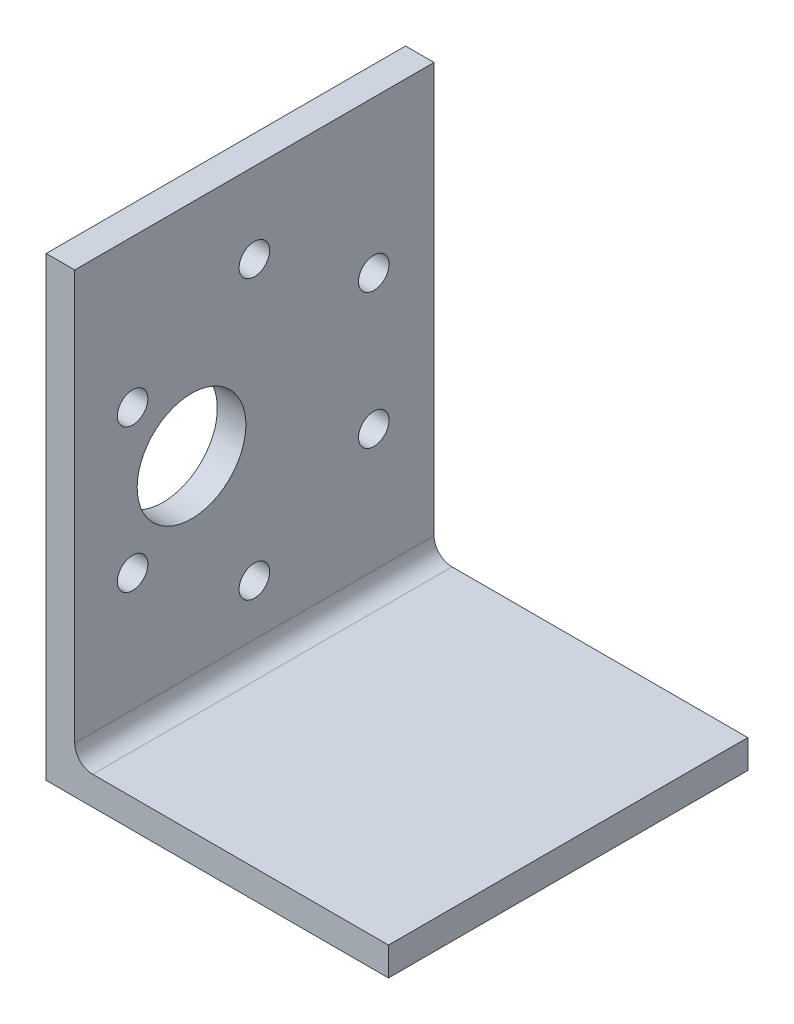
SolidWorks part; units mm, degrees
material "6061-T6 (SS)"
ref_plane "Front Plane" through (0, 0, 0) normal (0, 0, 1) x (1, 0, 0)
ref_plane "Top Plane" through (0, 0, 0) normal (0, 1, 0) x (1, 0, 0)
ref_plane "Right Plane" through (0, 0, 0) normal (1, 0, 0) x (0, 0, -1)
sketch "Sketch1" plane through (0, 0, 0) normal (0, 0, 1) x (1, 0, 0)
  line L0 (0, 0) -> (0, 50.8)
  line L1 (0, 50.8) -> (3.175, 50.8)
  line L2 (3.175, 50.8) -> (3.175, 3.175)
  line L3 (3.175, 3.175) -> (38.1, 3.175)
  line L4 (38.1, 3.175) -> (38.1, 0)
  line L5 (38.1, 0) -> (0, 0)
  dimension "D1" = 3.175
  dimension "D2" = 3.175
  dimension "D3" = 38.1
  dimension "D4" = 50.8
extrude "Boss-Extrude1" add sketch "Sketch1" along normal mid plane 40
fillet "Fillet1" radius 2 1 edges at (3.175, 3.175, 0)
sketch "Sketch10" plane through (0, 0, 0) normal (-1, 0, 0) x (0, 0, 1)
  line L0 (20, 0) -> (-20, 0) construction
  circle A0 centre (0.2647, 26.35) radius 15.5
  point P0 (0, 41.8477)
  point P2 (13.5538, 34.3281)
  point P4 (-13.2891, 18.8304)
  point P6 (0, 10.8523)
  point P17 (-13.2891, 33.8696)
  point P19 (13.5538, 18.3719)
  dimension "D1" = 31
  dimension "D2" = 60
  dimension "D3" = 60
  dimension "D4" = 26.35
hole_wizard "M3 Clearance Hole1" positions "Sketch10" profile "Sketch3" hole size "M3" standard "ANSI Metric" end condition through all
sketch "Sketch3" plane through (0, 41.8477, 0) normal (0, 1, 0) x (0, 0, 1)
  line L0 (0, 0) -> (0, 38.1)
  line L1 (0, 38.1) -> (1.7, 38.1)
  line L2 (1.7, 38.1) -> (1.7, 0)
  line L5 (1.7, 0) -> (0, 0)
  line L11 (0, -6.35) -> (0, 107.95) construction
  dimension "Thru Hole Dia." = 3.4
  dimension "Thru Hole Depth" = 38.1
sketch "Sketch6" plane through (0, 0, 0) normal (-1, 0, 0) x (0, 0, 1)
  line L0 (20, 0) -> (-20, 0) construction
  circle A0 centre (7, 26.35) radius 6.05
  circle A3 centre (0, 41.8477) radius 1.7 construction
  point P2 (4.8959, 25.4)
  dimension "D2" = 12.1
  dimension "D1" = 26.35
  dimension "D3" = 7
extrude "Cut-Extrude1" cut sketch "Sketch6" against normal through all
